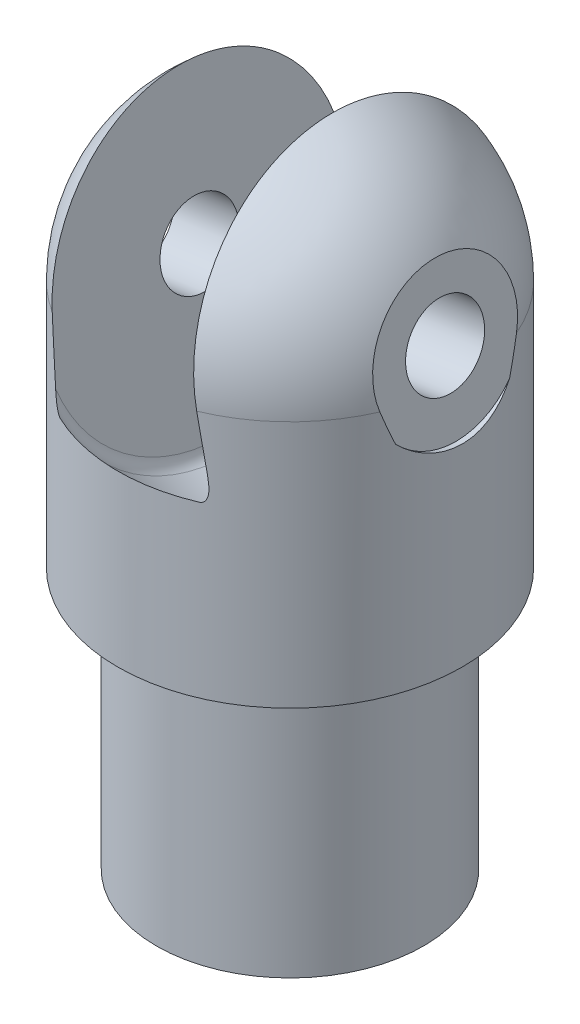
SolidWorks part; units mm, degrees
ref_plane "Front Plane" through (0, 0, 0) normal (0, 0, 1) x (1, 0, 0)
ref_plane "Top Plane" through (0, 0, 0) normal (0, 1, 0) x (1, 0, 0)
ref_plane "Right Plane" through (0, 0, 0) normal (1, 0, 0) x (0, 0, -1)
sketch "Sketch1" plane through (0, 0, 0) normal (0, 1, 0) x (1, 0, 0)
  circle A0 centre (0, 0) radius 12.9921
extrude "Boss-Extrude1" add sketch "Sketch1" along normal blind 25.4 contours A0
sketch "Sketch2" plane through (0, 0, 0) normal (1, 0, 0) x (0, 0, -1)
  line L0 (-16.764, 25.4) -> (-16.764, 49.53)
  line L1 (0, 25.4) -> (-16.764, 25.4)
  line L4 (12.9921, 25.4) -> (-12.9921, 25.4) construction
  line L5 (0, 14.2913) -> (0, -14.2913) construction
  line L6 (0, 25.4) -> (0, 66.294)
  arc A0 (0, 66.294) -> (-16.764, 49.53) centre (0, 49.53) ccw
  dimension "D1" = 33.528
  dimension "D2" = 24.13
revolve "Revolve1" add sketch "Sketch2" angle 360 about L6
ref_plane "Plane2" through (0, 49.53, 0) normal (0, -1, 0) x (-1, 0, 0)
ref_axis "Axis1" through (0, 49.53, 23.7) along (0, 0, -1)
ref_plane "Plane3" through (-6.8262, 48.5706, 0) normal (0.1392, -0.9903, 0) x (0, 0, -1)
ref_plane "Plane4" through (6.8262, 0.9594, 0) normal (-0.9903, -0.1392, 0) x (0, 0, -1)
sketch "Sketch3" plane through (-6.8556, 98.3102, 0) normal (-0.9903, -0.1392, 0) x (0, 0, -1)
  line L1 (-23.7, 49.2596) -> (13.1808, 49.2596) construction
  line L2 (0, 49.2596) -> (0, 73.1547) construction
  circle A2 centre (0, 49.2596) radius 3.81
  dimension "D1" = 7.62
extrude "Cut-Extrude1" cut sketch "Sketch3" against normal through all both and the other way through all
ref_axis "Axis2" through (17.2724, 51.9575, 0) along (-0.9903, -0.1392, 0)
sketch "Sketch10" plane through (0, 0, 0) normal (0, 0, 1) x (1, 0, 0)
  line L0 (17.2724, 51.9575) -> (-17.3227, 47.0954) construction
  line L1 (-8.8035, 48.2928) -> (6.2882, 50.4137)
  point P5 (-1.2576, 49.3533)
  dimension "D1" = 15.24
  dimension "D2" = 1.27
sketch "Sketch11" plane through (0, 0, 0) normal (0, 0, 1) x (1, 0, 0)
  line L2 (-8.8035, 48.2928) -> (6.2882, 50.4137) construction
  line L3 (-8.8035, 48.2928) -> (-11.0479, 64.2628)
  line L4 (6.2882, 50.4137) -> (3.8825, 67.5311)
  line L5 (-8.8035, 48.2928) -> (6.2882, 50.4137)
  arc A0 (3.8825, 67.5311) -> (-11.0479, 64.2628) centre (0, 49.53) ccw
  arc A1 (15.6362, 55.575) -> (-16.6967, 51.0309) centre (0, 49.53) ccw construction
  dimension "D1" = 18.415
revolve "Cut-Revolve10" cut sketch "Sketch11" angle 90 about axis through (17.2724, 51.9575, 0) along (-0.9903, -0.1392, 0) other way angle 180
sketch "Sketch13" plane through (0, 0, 0) normal (0, 0, 1) x (1, 0, 0)
  line L0 (-9.3337, 52.0657) -> (5.758, 54.1867)
  line L1 (-8.9774, 49.53) -> (-10.7815, 62.3671) construction
  line L2 (4.129, 65.7776) -> (6.4124, 49.53) construction
  line L3 (-8.8035, 48.2928) -> (6.2882, 50.4137) construction
  line L4 (-9.3337, 52.0657) -> (-11.6669, 68.667)
  line L5 (5.758, 54.1867) -> (3.4248, 70.788)
  arc A0 (3.4248, 70.788) -> (-11.6669, 68.667) centre (-1.7879, 53.1262) ccw
  dimension "D1" = 3.81
  dimension "D2" = 36.83
revolve "Cut-Revolve11" cut sketch "Sketch13" angle 360 about L0 other way angle 360
sketch "Sketch14" plane through (0, 0, 0) normal (0, 0, 1) x (1, 0, 0)
  line L0 (-8.8035, 48.2928) -> (6.2882, 50.4137) construction
  line L1 (-8.8035, 48.2928) -> (-7.7644, 40.8994)
  line L2 (6.2882, 50.4137) -> (7.3273, 43.0204)
  line L3 (-8.8035, 48.2928) -> (6.2882, 50.4137)
  arc A0 (-7.7644, 40.8994) -> (7.3273, 43.0204) centre (-1.2576, 49.3533) ccw
  dimension "D1" = 21.336
extrude "Cut-Extrude4" cut sketch "Sketch14" against normal blind 32.004
fillet "Fillet1" radius 1.27 6 edges at (-6.9258, 34.9325, 8.8351) (-7.2001, 36.8838, -6.7827) (-7.7644, 40.8994, -13.6315) (7.3273, 43.0204, -13.7417) (7.8916, 39.0048, -6.7827) (8.3694, 35.6053, 8.6699)
ref_plane "Plane5" through (-8.2655, -1.1616, 0) normal (-0.9903, -0.1392, 0) x (0, 0, -1)
sketch "Sketch15" plane through (-8.2655, -1.1616, 0) normal (-0.9903, -0.1392, 0) x (0, 0, -1)
  circle A0 centre (0, -49.048) radius 7.62
  dimension "D1" = 15.24
extrude "Cut-Extrude5" cut sketch "Sketch15" along normal blind 10.16
mirror "Mirror1" about plane through (6.8262, 0.9594, 0) normal (-0.9903, -0.1392, 0) of "Cut-Extrude5"
